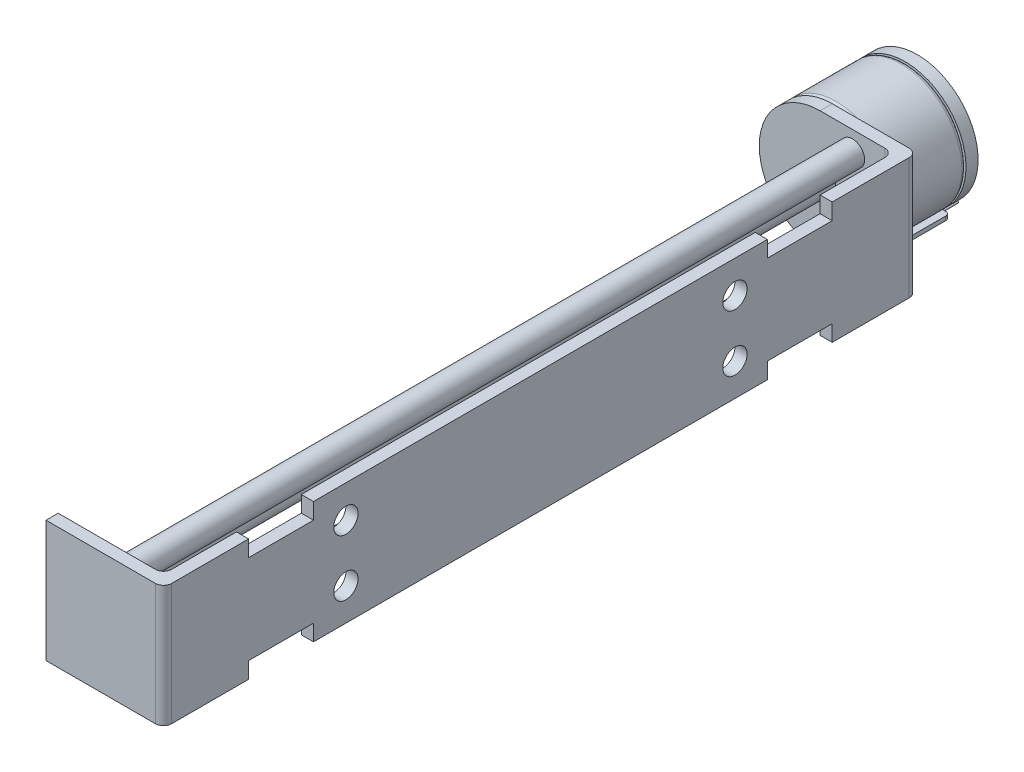
SolidWorks part; units mm, degrees
ref_plane "前视基准面" through (0, 0, 0) normal (0, 0, 1) x (1, 0, 0)
ref_plane "上视基准面" through (0, 0, 0) normal (0, 1, 0) x (1, 0, 0)
ref_plane "右视基准面" through (0, 0, 0) normal (1, 0, 0) x (0, 0, -1)
sketch "草图1" plane through (0, 0, 0) normal (0, 0, 1) x (1, 0, 0)
  circle A0 centre (0, 0) radius 1.5
  dimension "D1" = 3
extrude "凸台-拉伸1" add sketch "草图1" along normal blind 90
cosmetic thread "装饰螺纹线1" parameters "D2"=2.459
sketch "草图2" plane through (0, 0, 90) normal (0, 0, 1) x (1, 0, 0)
  circle A0 centre (0, 0) radius 1
  dimension "D1" = 2
extrude "凸台-拉伸2" add sketch "草图2" along normal blind 3
chamfer "倒角1" distance 1 angle 45 1 edges at (1, 0, 90)
sketch "草图3" plane through (0, 0, 0) normal (0, 0, -1) x (-1, 0, 0)
  circle A0 centre (0, 0) radius 7.5
  dimension "D1" = 15
extrude "凸台-拉伸3" add sketch "草图3" along normal blind 9
fillet "圆角1" radius 0.5 2 edges at (-7.5, 0, -9) (-7.5, 0, 0)
sketch "草图4" plane through (0, 0, 0) normal (0, 0, 1) x (1, 0, 0)
  line L0 (0, 7.5) -> (10.5, 7.5)
  line L1 (10.5, 7.5) -> (10.5, -7.5)
  line L2 (10.5, -7.5) -> (0, -7.5)
  circle A0 centre (0, 0) radius 2
  arc A1 (0, 7.5) -> (0, -7.5) centre (0, 0) ccw
  dimension "D1" = 4
  dimension "D2" = 15
  dimension "D3" = 10.5
extrude "凸台-拉伸4" add sketch "草图4" along normal blind 1.5
sketch "草图5" plane through (0, 0, -9) normal (0, 0, -1) x (-1, 0, 0)
  circle A0 centre (0, 0) radius 7.5
  dimension "D1" = 15
extrude "凸台-拉伸5" add sketch "草图5" along normal blind 1.5
sketch "草图7" plane through (0, -7.5, 0) normal (0, -1, 0) x (1, 0, 0)
  line L0 (10.5, 1.5) -> (10.5, 93)
  line L1 (10.5, 93) -> (-4, 93)
  line L2 (-4, 93) -> (-4, 91.5)
  line L3 (-4, 91.5) -> (9, 91.5)
  line L4 (9, 91.5) -> (9, 1.5)
  line L5 (0, 1.5) -> (10.5, 1.5) construction
  line L6 (0, 0) -> (10.5, 0) construction
  line L7 (10.5, 1.5) -> (10.5, 0) construction
  line L8 (9, 1.5) -> (10.5, 1.5)
  dimension "D1" = 93
  dimension "D2" = 1.5
  dimension "D3" = 1.5
  dimension "D4" = 14.5
extrude "凸台-拉伸6" add sketch "草图7" against normal blind 15
fillet "圆角2" radius 1 4 edges at (9, 0, 1.5) (9, 0, 91.5) (10.5, 0, 93) (10.5, 0, 0)
sketch "草图8" plane through (10.5, 0, 0) normal (1, 0, 0) x (0, 0, -1)
  line L0 (-101.8607, 0) -> (21.3286, 0) construction
  line L1 (-82.5, -7.5) -> (-82.5, -5.5)
  line L2 (-92, -7.5) -> (-1, -7.5) construction
  line L3 (-82.5, -5.5) -> (-74.5, -5.5)
  line L4 (-74.5, -5.5) -> (-74.5, -7.5)
  line L5 (-93, -7.5) -> (-93, 7.5) construction
  line L6 (-74.5, 5.5) -> (-74.5, 7.5)
  line L7 (-82.5, 5.5) -> (-74.5, 5.5)
  line L8 (-82.5, 7.5) -> (-82.5, 5.5)
  line L9 (-82.5, -7.5) -> (-74.5, -7.5)
  line L10 (-82.5, 7.5) -> (-74.5, 7.5)
  line L11 (-46.5, -43.5336) -> (-46.5, 59.6113) construction
  line L13 (-18.5, 5.5) -> (-18.5, 7.5)
  line L14 (-10.5, 7.5) -> (-10.5, 5.5)
  line L15 (-10.5, 5.5) -> (-18.5, 5.5)
  line L16 (-18.5, -5.5) -> (-18.5, -7.5)
  line L17 (-10.5, -7.5) -> (-18.5, -7.5)
  line L18 (-10.5, -5.5) -> (-18.5, -5.5)
  line L19 (-10.5, -7.5) -> (-10.5, -5.5)
  circle A0 centre (-70.5, -3.5) radius 1.5
  circle A1 centre (-70.5, 3.5) radius 1.5
  circle A2 centre (-22.5, 3.5) radius 1.5
  circle A3 centre (-22.5, -3.5) radius 1.5
  line M10 (-1, 7.5) -> (-92, 7.5)
  line M12 (-92, -7.5) -> (-1, -7.5)
  dimension "D4" = 3
  dimension "D1" = 10.5
  dimension "D2" = 8
  dimension "D3" = 2
  dimension "D5" = 3.5
  dimension "D6" = 22.5
  dimension "D7" = 46.5
extrude "切除-拉伸1" cut sketch "草图8" against normal blind 3 contours L4 L3 L1 M12 | L8 L7 L6 M10 | A0 | A1 | A3 | L19 L18 L16 M12 | L15 L14 L13 M10 | A2 region at (10.5, -6.5, 14.5) region at (10.5, -6.5, 78.5) region at (10.5, 6.5, 78.5) region at (10.5, 6.5, 14.5) region at (10.5, -3.5, 70.5) region at (10.5, 3.5, 70.5) region at (10.5, -3.5, 22.5)
sketch "草图9" plane through (0, 0, 93) normal (0, 0, 1) x (1, 0, 0)
  line L0 (11.6988, 0) -> (-6.7822, 0) construction
  line L1 (10.5, 7.5) -> (10.5, -7.5) construction
  circle A0 centre (4, -5) radius 1.5
  circle A1 centre (4, 5) radius 1.5
  dimension "D1" = 3
  dimension "D2" = 6.5
  dimension "D3" = 5
extrude "凸台-拉伸7" add sketch "草图9" against normal up to surface (91.5 mm away) up to face at (2.125, 0, 1.5)
ref_plane "基准面1" through (0, -7.5, 0) normal (0, -1, 0) x (-1, 0, 0)
sketch "草图10" plane through (0, -7.5, 0) normal (0, -1, 0) x (-1, 0, 0)
  line L0 (12.7557, 4.5) -> (-21.2612, 4.5) construction
  line L1 (0, 0) -> (-9.5, 0) construction
  line L2 (0, 14.9986) -> (0, -6.7339) construction
  line L4 (4, 10.5) -> (-4, 10.5)
  line L5 (4, 10.5) -> (4, 2.5)
  line L6 (4, 2.5) -> (-4, 2.5)
  line L7 (-4, 10.5) -> (-4, 2.5)
  line L8 (4, 10.5) -> (-4, 2.5) construction
  line L9 (4, 2.5) -> (-4, 10.5) construction
  point P7 (0, 6.5)
  dimension "D1" = 4.5
  dimension "D2" = 8
  dimension "D3" = 8
  dimension "D4" = 2
extrude "凸台-拉伸8" add sketch "草图10" along normal blind 0.5 separate body
sketch "草图12" plane through (0, 0, -10.5) normal (0, 0, -1) x (-1, 0, 0)
  line L0 (0, -9.0938) -> (0, -6.2199) construction
  line L1 (4.2027, -7.75) -> (-4.6939, -7.75) construction
  line L2 (4, -8) -> (-4, -8) construction
  circle A0 centre (1, -7.75) radius 0.1
  circle A1 centre (3, -7.75) radius 0.1
  circle A2 centre (-1, -7.75) radius 0.1
  circle A3 centre (-3, -7.75) radius 0.1
  dimension "D2" = 0.2
  dimension "D1" = 0.25
  dimension "D3" = 1
  dimension "D4" = 2
extrude "凸台-拉伸9" add sketch "草图12" along normal blind 2
fillet "圆角3" radius 0.5 4 edges at (-4, -7.75, -10.5) (4, -7.75, -10.5) (4, -7.75, -2.5) (-4, -7.75, -2.5)
